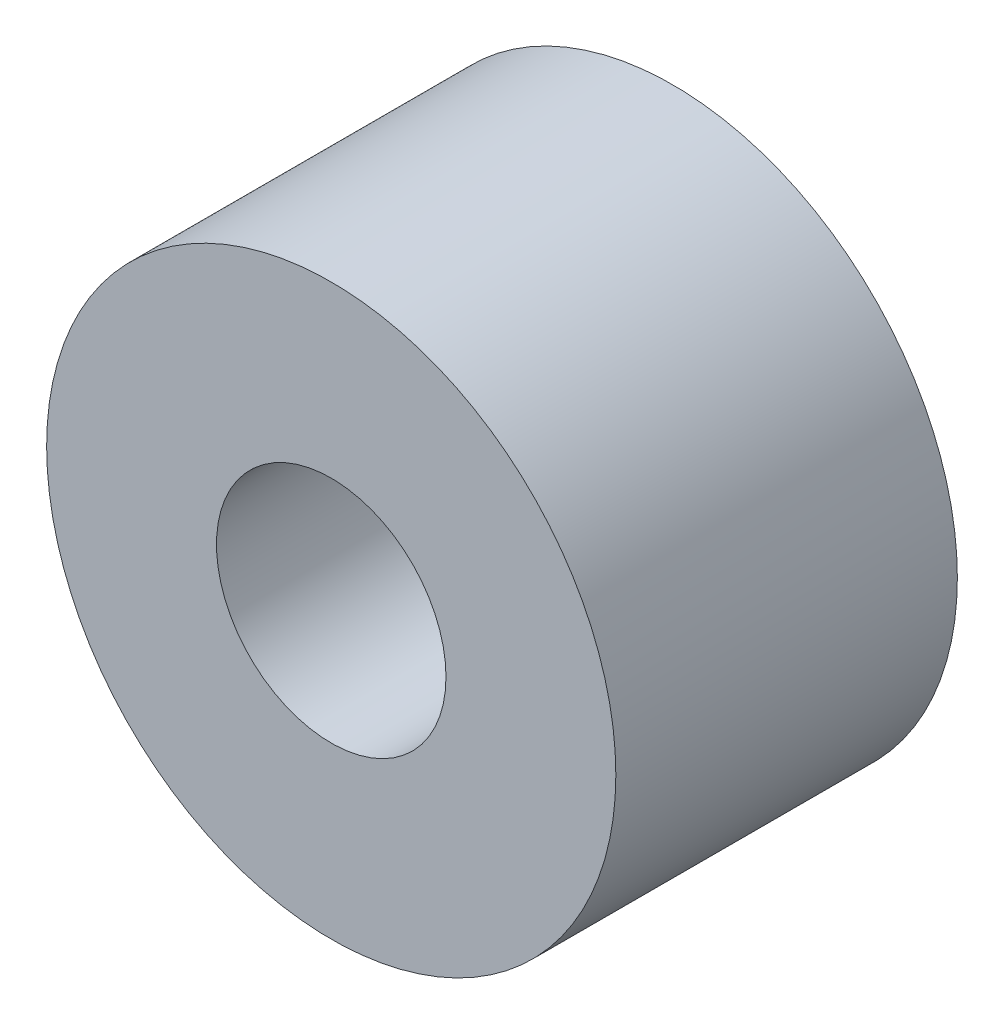
SolidWorks part; units mm, degrees
ref_plane "Front Plane" through (0, 0, 0) normal (0, 0, 1) x (1, 0, 0)
ref_plane "Top Plane" through (0, 0, 0) normal (0, 1, 0) x (1, 0, 0)
ref_plane "Right Plane" through (0, 0, 0) normal (1, 0, 0) x (0, 0, -1)
sketch "Sketch1" plane through (0, 0, 0) normal (0, 0, 1) x (1, 0, 0)
  circle A0 centre (0, 0) radius 7.9375
  circle A1 centre (0, 0) radius 3.2004
  dimension "OD" = 15.875
  dimension "ID" = 6.4008
extrude "Extrude1" add sketch "Sketch1" along normal mid plane 9.525
sketch "Sketch2" plane through (0, 0, 0) normal (1, 0, 0) x (0, 0, -1)
  line L0 (-4.7625, -3.2004) -> (4.7625, -3.2004) construction
  line L3 (4.7625, 3.2004) -> (-4.7625, 3.2004) construction
  line L5 (-4.7625, -3.2004) -> (4.7625, -3.2004)
  line L6 (4.7625, 3.2004) -> (-4.7625, 3.2004)
sketch "Sketch4" plane through (0, 0, 4.7625) normal (0, 0, 1) x (1, 0, 0)
  line L0 (0, 0) -> (-2.263, 2.263)
  line L1 (0, -55) -> (0, 55) construction
  circle A0 centre (0, 0) radius 3.2004 construction
  dimension "D1" = 45
ref_axis "Axis1" through (0, 0, 4.7625) along (0, 0, -1)
